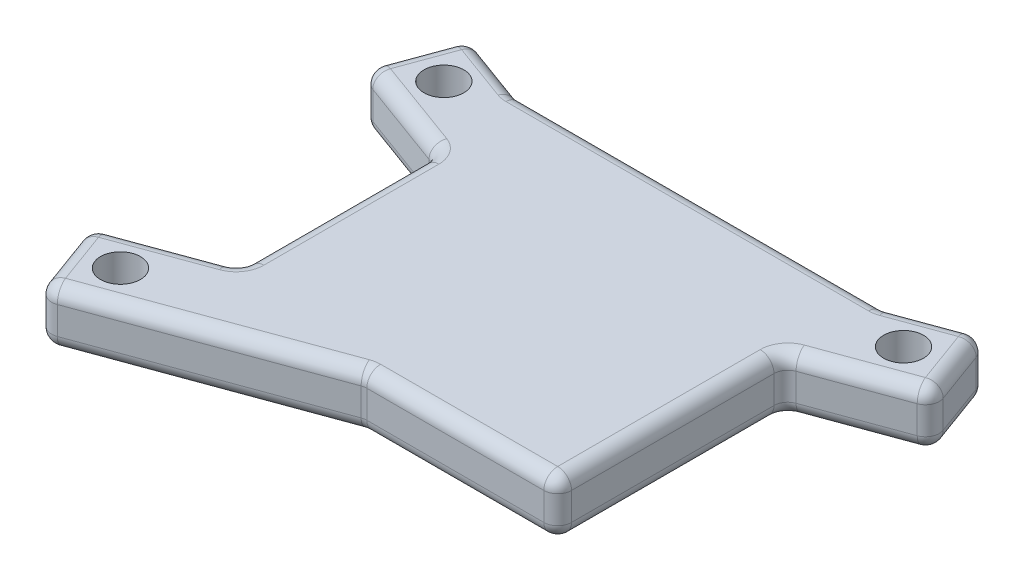
SolidWorks part; units mm, degrees
ref_plane "Front Plane" through (0, 0, 0) normal (0, 0, 1) x (1, 0, 0)
ref_plane "Top Plane" through (0, 0, 0) normal (0, 1, 0) x (1, 0, 0)
ref_plane "Right Plane" through (0, 0, 0) normal (1, 0, 0) x (0, 0, -1)
sketch "Sketch1" plane through (0, 0, 0) normal (0, 1, 0) x (1, 0, 0)
  line L0 (21.2293, -21.8246) -> (29.5896, -24.8839)
  line L1 (29.5896, -24.8839) -> (71.7276, -24.8839)
  line L2 (71.7276, -24.8839) -> (80.0879, -21.8246)
  line L3 (80.0879, -21.8246) -> (83.3611, -30.7695)
  line L4 (83.3611, -30.7695) -> (70.6611, -35.4168)
  line L5 (70.6611, -35.4168) -> (70.6611, -61.3274)
  line L7 (30.6561, -57.7105) -> (30.6561, -35.4168)
  line L8 (30.6561, -35.4168) -> (17.9561, -30.7695)
  line L9 (17.9561, -30.7695) -> (21.2293, -21.8246)
  line L12 (55.1375, -61.3274) -> (69.8674, -61.3274) construction
  line L13 (30.6561, -57.7105) -> (17.9561, -62.3578)
  line L14 (-48.9224, -86.8307) -> (30.1351, -57.9011) construction
  line L15 (17.9561, -62.3578) -> (21.2293, -71.3027)
  line L16 (50.6586, -60.5337) -> (-49.8568, -97.3153) construction
  line L17 (21.2293, -71.3027) -> (48.4895, -61.3274)
  line L18 (48.4895, -61.3274) -> (70.6611, -61.3274)
  line L19 (71.7276, -24.8839) -> (151.174, 4.188) construction
  line L20 (150.2396, -6.2966) -> (71.1821, -35.2262) construction
  line L21 (70.6611, -35.9716) -> (70.6611, -57.1557) construction
  line L25 (30.6561, -57.1557) -> (30.6561, -35.9716) construction
  line L26 (30.1351, -35.2262) -> (-48.9224, -6.2966) construction
  line L29 (-49.8568, 4.188) -> (29.5896, -24.8839) construction
  point P2 (29.8624, -20.4108)
  point P10 (87.1921, -11.042)
  point P20 (68.6363, -20.9183)
  point P25 (71.7276, -20.3625)
  point P26 (70.8656, -20.6779)
  point P27 (48.4895, -56.806)
  point P32 (29.5896, -20.3625)
  point P33 (71.7276, -20.3625)
  point P34 (29.5896, -20.3625)
  point P35 (29.5896, -20.3625)
  point P36 (71.7276, -20.3625)
  point P39 (88.2437, -14.3188)
  point P40 (70.8043, -30.9955)
  point P44 (70.8043, -30.9955)
  point P48 (29.2978, -53.3502)
  point P49 (30.6561, -52.6343)
  point P50 (0, 0)
  dimension "D1" = 12.7
  dimension "D2" = 12.7
  dimension "D3" = 12.7
extrude "Boss-Extrude1" add sketch "Sketch1" along normal blind 6.35
sketch "Sketch2" plane through (0, 6.35, 0) normal (0, 1, 0) x (1, 0, 0)
  line L0 (30.6561, -35.4168) -> (30.6561, -57.7105) construction
  line L1 (70.6611, -61.3274) -> (70.6611, -35.4168) construction
  line L2 (24.3061, -65.1055) -> (25.9427, -69.578) construction
  line L3 (21.2293, -71.3027) -> (48.4895, -61.3274) construction
  line L4 (24.3061, -65.1055) -> (22.6695, -60.633) construction
  line L5 (30.6561, -57.7105) -> (17.9561, -62.3578) construction
  line L6 (24.3061, -28.0218) -> (22.6695, -32.4943) construction
  line L7 (17.9561, -30.7695) -> (30.6561, -35.4168) construction
  line L8 (24.3061, -28.0218) -> (25.9427, -23.5494) construction
  line L9 (29.5896, -24.8839) -> (21.2293, -21.8246) construction
  line L10 (77.0111, -28.0218) -> (75.3745, -23.5494) construction
  line L11 (80.0879, -21.8246) -> (71.7276, -24.8839) construction
  line L12 (77.0111, -28.0218) -> (78.6477, -32.4943) construction
  line L14 (70.6611, -35.4168) -> (83.3611, -30.7695) construction
  circle A9 centre (77.0111, -28.0218) radius 2.286
  circle A10 centre (24.3061, -65.1055) radius 2.286
  circle A11 centre (24.3061, -28.0218) radius 2.286
  point P16 (79.1071, -32.3262)
  point P29 (0, 0)
  dimension "D1" = 6.35
  dimension "D4" = 4.572
  dimension "D2" = 6.35
  dimension "D3" = 6.35
extrude "Cut-Extrude1" cut sketch "Sketch2" against normal through all
fillet "Fillet1" radius 1.5875 39 edges at (77.0111, 6.35, 33.0932) (77.0111, 0, 33.0932) (24.3061, 6.35, 33.0932) (24.3061, 0, 33.0932) (24.3061, 6.35, 60.0341) (24.3061, 0, 60.0341) (75.9078, 6.35, 23.3542) (75.9078, 0, 23.3542) (25.4095, 0, 23.3542) (59.5753, 6.35, 61.3274) (59.5753, 0, 61.3274) (70.6611, 3.175, 61.3274) (70.6611, 6.35, 48.3721) (70.6611, 3.175, 35.4168) (70.6611, 0, 48.3721) (21.2293, 3.175, 21.8246) (19.5927, 6.35, 26.297) (17.9561, 3.175, 30.7695) (19.5927, 0, 26.297) (17.9561, 3.175, 62.3578) (19.5927, 6.35, 66.8303) (19.5927, 0, 66.8303) (30.6561, 3.175, 35.4168) (30.6561, 6.35, 46.5637) (30.6561, 3.175, 57.7105) (30.6561, 0, 46.5637) (71.7276, 3.175, 24.8839) (50.6586, 6.35, 24.8839) (29.5896, 3.175, 24.8839) (50.6586, 0, 24.8839) (83.3611, 3.175, 30.7695) (81.7245, 6.35, 26.297) (80.0879, 3.175, 21.8246) (81.7245, 0, 26.297) (21.2293, 3.175, 71.3027) (34.8594, 6.35, 66.3151) (48.4895, 3.175, 61.3274) (34.8594, 0, 66.3151) (25.4095, 6.35, 23.3542)
sketch "Sketch3" plane through (0, 0, 0) normal (0, -1, 0) x (1, 0, 0)
  line L0 (30.6561, 36.5264) -> (30.6561, 56.601) construction
  line L1 (71.4463, 24.8839) -> (29.8709, 24.8839) construction
  circle A0 centre (50.6586, 40.7589) radius 2.286
  dimension "D3" = 4.572
  dimension "D1" = 20.0025
  dimension "D2" = 15.875
extrude "Cut-Extrude2" cut sketch "Sketch3" against normal blind 3.175
